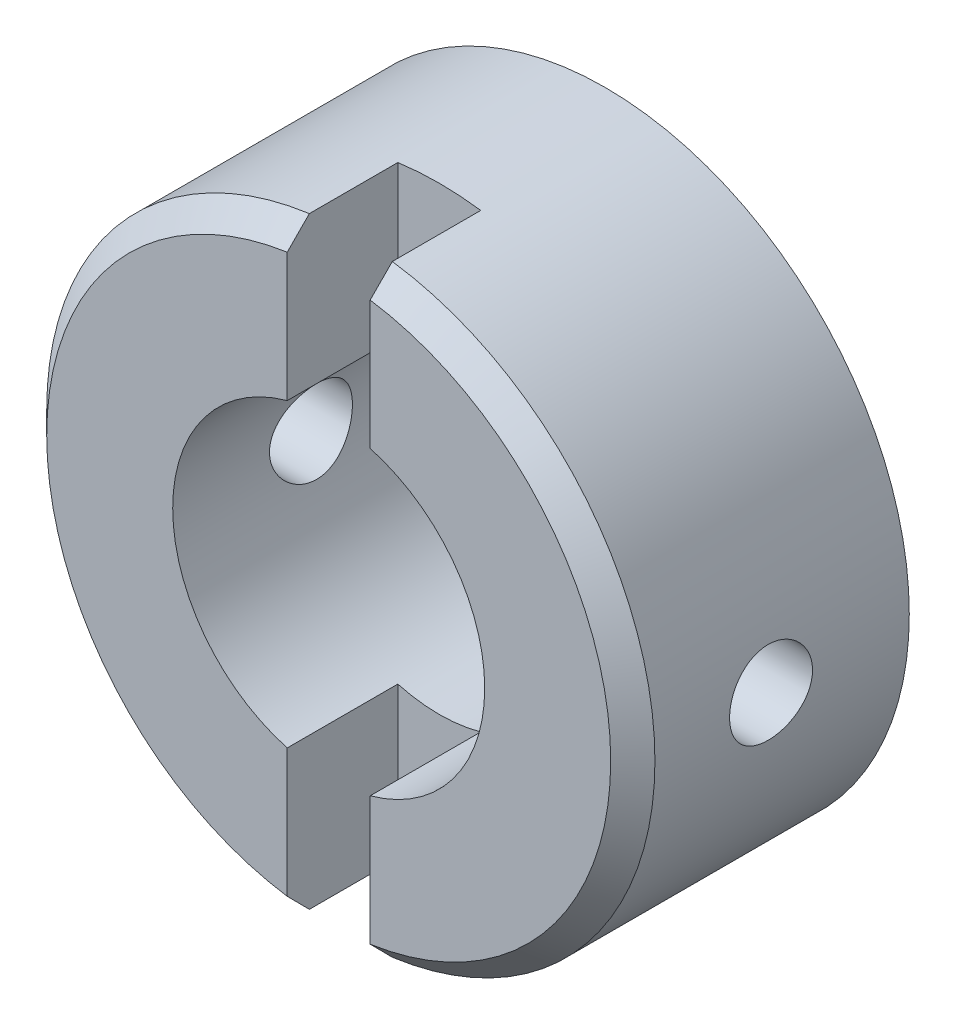
SolidWorks part; units mm, degrees
ref_plane "Front" through (0, 0, 0) normal (0, 0, 1) x (1, 0, 0)
ref_plane "Top" through (0, 0, 0) normal (0, 1, 0) x (1, 0, 0)
ref_plane "Right" through (0, 0, 0) normal (1, 0, 0) x (0, 0, -1)
sketch "Sketch1" plane through (0, 0, 0) normal (0, 0, 1) x (1, 0, 0)
  circle A0 centre (0, 0) radius 11
  circle A1 centre (0, 0) radius 5.6429
  dimension "D1" = 11.2857
extrude "BaseNut" add sketch "Sketch1" against normal blind 10
cosmetic thread "ThreadCosmetic1" [suppressed] parameters "D2"=13
chamfer "Chamfer1" distance 0.8 angle 45 1 edges at (11, 0, 0)
sketch "Sketch2" plane through (-6.0929, -5.3641, 0) normal (0, 0, 1) x (1, 0, 0)
  line L0 (6.0929, 17.6245) -> (6.0929, -7.073) construction
  line L1 (4.5929, 16.2613) -> (4.5929, -5.5332)
  line L2 (7.5929, 16.2613) -> (7.5929, -5.5332)
  arc A1 (7.5929, 16.2613) -> (4.5929, 16.2613) centre (6.0929, 5.3641) ccw
  arc A2 (4.5929, -5.5332) -> (7.5929, -5.5332) centre (6.0929, 5.3641) ccw
  circle A3 centre (6.0929, 5.3641) radius 11 construction
  dimension "n" = 3
extrude "Cut-Extrude1" cut sketch "Sketch2" against normal offset from surface (4 mm away) 6 up to face at (5.6429, 0, -10)
sketch "Sketch3" plane through (0, 0, 0) normal (1, 0, 0) x (0, 0, -1)
  line L4 (10, -11) -> (10, 11) construction
  circle A0 centre (5, 0) radius 1.5
  dimension "d2" = 3
  dimension "K" = 5
extrude "Cut-Extrude2" cut sketch "Sketch3" against normal through all and the other way through all
cosmetic thread "ThreadCosmetic2" [suppressed] parameters "D2"=4
cosmetic thread "ThreadCosmetic3" [suppressed] parameters "D2"=4
chamfer "EndChamfer" distance 0.4 angle 45 1 edges at (5.6429, 0, -10)
sketch "Sketch4" plane through (0, 0, 0) normal (0, 1, 0) x (1, 0, 0)
  line L0 (4.7857, 10.0286) -> (4.7857, 9.1714)
  line L1 (4.7857, 9.1714) -> (5.6429, 9.1714)
  line L2 (5.6429, 9.1714) -> (6.3852, 9.6)
  line L3 (6.3852, 9.6) -> (5.6429, 10.0286)
  line L4 (5.6429, 10.0286) -> (4.7857, 10.0286)
  line L5 (0, 13.0642) -> (0, -2.5632) construction
  line L7 (5.6429, 9.6) -> (-5.6429, 9.6) construction
  dimension "D1" = 0.8571
  dimension "D2" = 11.2857
revolve "Cut-Revolve10" [suppressed] cut sketch "Sketch4" angle 360 about L5
pattern_linear "LPattern10" [suppressed] count 10 spacing 1.0286 along (0, 0, 1) of bodies 104
equation "\"D1@EndChamfer\" = \"C@Chamfer1\" / 2"
equation "\"D2@ThreadCosmetic3\" = \"D2@ThreadCosmetic2\""
equation "\"D1@Sketch4\" =  ( \"D2@ThreadCosmetic1\" - \"D1@Sketch1\" )  / 2"
equation "\"D3@LPattern10\" = \"D1@Sketch4\" * 1.2"
equation "\"D1@LPattern10\" = \"m@BaseNut\" / \"D3@LPattern10\""
equation " \"D2@Sketch4\"=\"D1@Sketch1\" "
